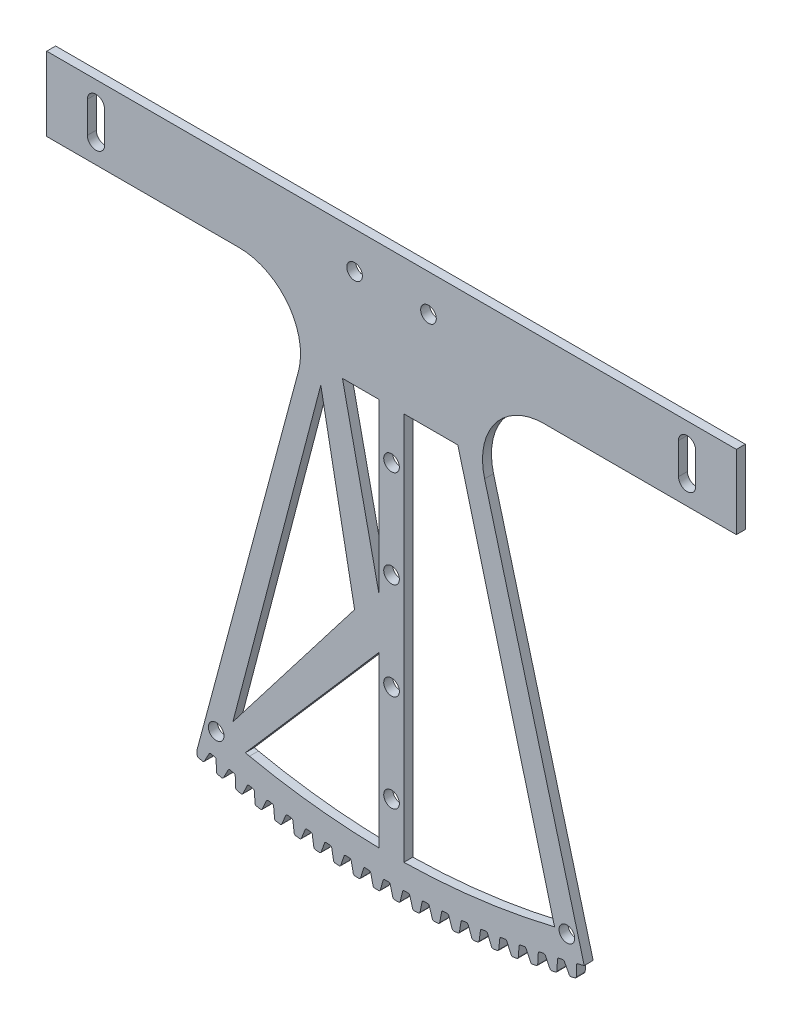
SolidWorks part; units mm, degrees
material "201 Annealed Stainless Steel (SS)"
ref_plane "Front Plane" through (0, 0, 0) normal (0, 0, 1) x (1, 0, 0)
ref_plane "Top Plane" through (0, 0, 0) normal (0, 1, 0) x (1, 0, 0)
ref_plane "Right Plane" through (0, 0, 0) normal (1, 0, 0) x (0, 0, -1)
sketch "Sketch3" plane through (0, 0, 0) normal (0, 0, 1) x (1, 0, 0)
  line L0 (0, 0) -> (0, -304.8) construction
  line L1 (-21.234, -79.2464) -> (-78.888, -294.4142)
  line L2 (21.234, -79.2464) -> (78.888, -294.4142)
  line L4 (-140, -79.56) -> (140, -79.56)
  line L5 (-140, -79.56) -> (-140, -109.56)
  line L6 (-140, -109.56) -> (140, -109.56)
  line L7 (140, -79.56) -> (140, -109.56)
  line L8 (0, -109.56) -> (0, -79.56) construction
  line L9 (-140, -94.56) -> (140, -94.56) construction
  arc A0 (-78.888, -294.4142) -> (78.888, -294.4142) centre (0, 0) ccw
  point P269 (0, -94.56)
  dimension "D1" = 304.8
  dimension "D4" = 79.56
  dimension "D5" = 30
  dimension "D6" = 280
  dimension "D7" = 140
extrude "Boss-Extrude2" add sketch "Sketch3" along normal blind 3.6286 contours L7 L4 L2 L6 | L1 L6 L2 L4 | L1 L4 L2 | L5 L6 L1 L4 | L1 A0 L2 L6 region at (0, -95.3531, 0) region at (-82.6452, -94.3847, 0) region at (0, -220.3694, 0) region at (82.6452, -94.3847, 0)
fillet "Fillet1" radius 25 2 edges at (-29.3565, -109.56, 1.8143) (29.3565, -109.56, 1.8143)
sketch "Sketch4" plane through (0, -79.56, 0) normal (0, 1, 0) x (1, 0, 0)
  line L1 (-140, 0) -> (140, 0)
  line L2 (-140, 0) -> (-140, -3.6286)
  line L3 (-140, -3.6286) -> (140, -3.6286)
  line L4 (140, 0) -> (140, -3.6286)
  line L5 (0, -3.6286) -> (0, 0) construction
  line L6 (-140, -1.8143) -> (140, -1.8143) construction
  point P252 (0, -1.8143)
sketch "Sketch5" plane through (0, 0, 0) normal (0, 0, -1) x (-1, 0, 0)
  line L0 (-123.5, -94.56) -> (-123.5, -100.91)
  line L1 (-116.5, -94.56) -> (-116.5, -100.91)
  line L2 (116.5, -94.56) -> (116.5, -88.21)
  line L3 (140, -79.56) -> (-140, -79.56) construction
  line L4 (-120, -88.21) -> (-120, -100.91) construction
  line L5 (0, -79.56) -> (0, -109.56) construction
  line L6 (-116.5, -94.56) -> (-116.5, -88.21)
  line L7 (-123.5, -94.56) -> (-123.5, -88.21)
  line L8 (116.5, -94.56) -> (116.5, -100.91)
  line L9 (123.5, -94.56) -> (123.5, -100.91)
  line L10 (123.5, -94.56) -> (123.5, -88.21)
  line L11 (-140, -79.56) -> (-140, -109.56) construction
  line L12 (120, -88.21) -> (120, -100.91) construction
  arc A1 (-116.5, -88.21) -> (-123.5, -88.21) centre (-120, -88.21) ccw
  arc A2 (-123.5, -100.91) -> (-116.5, -100.91) centre (-120, -100.91) ccw
  arc A3 (123.5, -100.91) -> (116.5, -100.91) centre (120, -100.91) cw
  arc A4 (116.5, -88.21) -> (123.5, -88.21) centre (120, -88.21) cw
  circle A5 centre (-15, -94.56) radius 3.175
  circle A6 centre (15, -94.56) radius 3.175
  dimension "D1" = 16.5
  dimension "D2" = 7
  dimension "D3" = 8.65
  dimension "D5" = 3.5
  dimension "D6" = 15
  dimension "D8" = 6.35
  dimension "D4" = 6.35
  dimension "D7" = 15
sketch "Sketch13" plane through (0, 0, 0) normal (0, 0, -1) x (-1, 0, 0)
  line L0 (0, 0) -> (78.888, -294.4142)
  line L1 (0, 0) -> (-78.888, -294.4142)
  arc A0 (-78.888, -294.4142) -> (78.888, -294.4142) centre (0, 0) ccw
  arc A1 (-78.888, -294.4142) -> (78.888, -294.4142) centre (0, 0) ccw construction
  arc A2 (-78.888, -294.4142) -> (78.888, -294.4142) centre (0, 0) ccw
  circle A3 centre (0, 0) radius 304.8
  dimension "D1" = 609.6
sketch "Sketch14" plane through (0, 0, 0) normal (0, 0, -1) x (-1, 0, 0)
  line L0 (0, 0) -> (80.0203, -298.6399) construction
  line L2 (78.888, -294.4142) -> (78.9109, -297.0369)
  line L3 (78.9109, -297.0369) -> (76.2891, -297.7211)
  line L18 (76.2891, -297.7211) -> (75.0275, -295.4216)
  line L20 (0, 0) -> (-79.2746, -295.8555) construction
  line L32 (78.888, -294.4142) -> (75.0275, -295.4216)
  line L33 (75.0275, -295.4216) -> (78.888, -294.4142)
  line L34 (0, 0) -> (-75.3952, -296.8678) construction
  line L35 (0, 0) -> (-71.5028, -297.8293) construction
  line L36 (0, 0) -> (-67.5982, -298.7397) construction
  line L37 (0, 0) -> (-63.6821, -299.5989) construction
  line L38 (0, 0) -> (-59.755, -300.4068) construction
  line L39 (0, 0) -> (-55.8176, -301.1633) construction
  line L40 (0, 0) -> (-51.8707, -301.8681) construction
  line L41 (0, 0) -> (-47.9149, -302.5212) construction
  line L42 (0, 0) -> (-43.951, -303.1225) construction
  line L43 (0, 0) -> (-39.9794, -303.6718) construction
  line L44 (0, 0) -> (-36.0011, -304.1691) construction
  line L45 (0, 0) -> (-32.0165, -304.6143) construction
  line L46 (0, 0) -> (-28.0265, -305.0073) construction
  line L47 (0, 0) -> (-24.0316, -305.348) construction
  line L48 (0, 0) -> (-20.0327, -305.6364) construction
  line L49 (0, 0) -> (-16.0303, -305.8724) construction
  line L50 (0, 0) -> (-12.0252, -306.0561) construction
  line L51 (0, 0) -> (-8.018, -306.1873) construction
  line L52 (0, 0) -> (-4.0094, -306.266) construction
  line L53 (0, 0) -> (-0.0002, -306.2922) construction
  line L54 (0, 0) -> (4.0091, -306.266) construction
  line L55 (0, 0) -> (8.0176, -306.1873) construction
  line L56 (0, 0) -> (12.0248, -306.0561) construction
  line L57 (0, 0) -> (16.03, -305.8725) construction
  line L58 (0, 0) -> (20.0323, -305.6364) construction
  line L59 (0, 0) -> (24.0313, -305.348) construction
  line L60 (0, 0) -> (28.0261, -305.0073) construction
  line L61 (0, 0) -> (32.0162, -304.6143) construction
  line L62 (0, 0) -> (36.0007, -304.1691) construction
  line L63 (0, 0) -> (39.9791, -303.6719) construction
  line L64 (0, 0) -> (43.9506, -303.1225) construction
  line L65 (0, 0) -> (47.9146, -302.5213) construction
  line L66 (0, 0) -> (51.8704, -301.8682) construction
  line L67 (0, 0) -> (55.8173, -301.1633) construction
  line L68 (0, 0) -> (59.7546, -300.4069) construction
  line L69 (0, 0) -> (63.6817, -299.599) construction
  line L70 (0, 0) -> (67.5979, -298.7398) construction
  line L71 (0, 0) -> (71.5025, -297.8293) construction
  line L72 (0, 0) -> (75.3948, -296.8679) construction
  line L73 (0, 0) -> (-79.2746, -295.8555) construction
  line L74 (0, 0) -> (-75.3952, -296.8678) construction
  line L137 (37.789, -141.0305) -> (78.888, -294.4142) construction
  line L138 (-140, -79.56) -> (-140, -109.56)
  line L139 (-140, -109.56) -> (-61.9371, -109.56)
  line L140 (-37.789, -141.0305) -> (-78.888, -294.4142)
  line L141 (78.888, -294.4142) -> (37.789, -141.0305)
  line L142 (61.9371, -109.56) -> (140, -109.56)
  line L143 (140, -109.56) -> (140, -79.56)
  line L144 (140, -79.56) -> (-140, -79.56)
  line L145 (-140, -79.56) -> (-140, -109.56)
  line L146 (-140, -109.56) -> (-61.9371, -109.56)
  line L147 (-37.789, -141.0305) -> (-78.888, -294.4142)
  line L149 (61.9371, -109.56) -> (140, -109.56)
  line L150 (140, -109.56) -> (140, -79.56)
  line L151 (140, -79.56) -> (-140, -79.56)
  circle A0 centre (0, 0) radius 307.34
  circle A1 centre (0, 0) radius 302.26
  arc A3 (-37.789, -141.0305) -> (-61.9371, -109.56) centre (-61.9371, -134.56) ccw
  arc A5 (61.9371, -109.56) -> (37.789, -141.0305) centre (61.9371, -134.56) ccw
  arc A6 (-37.789, -141.0305) -> (-61.9371, -109.56) centre (-61.9371, -134.56) ccw
  arc A8 (61.9371, -109.56) -> (37.789, -141.0305) centre (61.9371, -134.56) ccw
  arc A11 (-78.888, -294.4142) -> (78.888, -294.4142) centre (0, 0) ccw
  arc A12 (-78.888, -294.4142) -> (78.888, -294.4142) centre (0, 0) ccw
  arc M181 (-78.888, -294.4142) -> (78.888, -294.4142) centre (0, 0) ccw
  dimension "D5" = 614.68
  dimension "D6" = 30
  dimension "D7" = 40
  dimension "D4" = 604.52
  dimension "D1" = 14.5
  dimension "D3" = 14.5
  dimension "D8" = 0.75
  dimension "D9" = 306.2922
  dimension "D10" = 0.75
  dimension "D2" = 0
extrude "Boss-Extrude4" add sketch "Sketch14" against normal up to surface (3.6286 mm away) contours L2 M181 region at (-77.2591, -296.0724, 0) up to face at (0, -146.6727, 3.6286)
sketch "Sketch15" plane through (0, 0, 0) normal (1, 0, 0) x (0, 0, -1)
  line L0 (0, 0) -> (-23.3364, 0) construction
sketch "Sketch16" plane through (0, 0, 0) normal (0, 0, -1) x (-1, 0, 0)
  line L0 (75.0275, -295.4216) -> (73.7653, -293.1208)
  line L1 (73.7653, -293.1208) -> (71.1999, -293.7544)
  line L2 (71.1999, -293.7544) -> (71.1541, -296.3784)
  line L3 (0, 0) -> (71.5025, -297.8293) construction
  line L4 (0, 0) -> (75.3948, -296.8679) construction
  circle A0 centre (0, 0) radius 302.26 construction
  arc A1 (-78.888, -294.4142) -> (78.888, -294.4142) centre (0, 0) ccw construction
  dimension "D1" = 14.5
  dimension "D2" = 14.5
extrude "Cut-Extrude2" cut sketch "Sketch16" against normal through all and the other way through all
fillet "Fillet2" radius 0.7 2 edges at (-76.2891, -297.7211, 1.8143) (-78.9109, -297.0369, 1.8143)
pattern_circular "CirPattern8" count 20 every 1.5 about axis through (0, 0, 0) along (0, 0, 1) of "Cut-Extrude2", "Boss-Extrude4", "Fillet2"
extrude "Cut-Extrude3" cut sketch "Sketch5" against normal through all
sketch "Sketch17" plane through (0, 0, 0) normal (0, 0, -1) x (-1, 0, 0)
  line L0 (0, -79.56) -> (0, -134.56) construction
  line L1 (140, -79.56) -> (-140, -79.56) construction
  line L2 (-61.9371, -109.56) -> (61.9371, -109.56) construction
  line L3 (-36.9371, -134.56) -> (-26.9371, -134.56) construction
  line L4 (-36.9371, -134.56) -> (-26.9371, -134.56) construction
  line L5 (-26.9371, -134.56) -> (-66.1944, -284.3612) construction
  line L6 (-66.1944, -284.3612) -> (-76.1944, -284.3612) construction
  line L7 (0, -292.2593) -> (5, -292.2593) construction
  line L8 (-37.789, -141.0305) -> (-78.888, -294.4142) construction
  line L9 (0, -134.56) -> (-5, -134.56) construction
  line L10 (0, -134.56) -> (5, -134.56) construction
  line L11 (26.9371, -134.56) -> (36.9371, -134.56) construction
  line L12 (-5, -134.56) -> (-5, -292.2593) construction
  line L13 (36.9371, -134.56) -> (26.9371, -134.56) construction
  line L14 (26.9371, -134.56) -> (66.1944, -284.3612) construction
  line L15 (66.1944, -284.3612) -> (76.1944, -284.3612) construction
  line L16 (37.789, -141.0305) -> (78.888, -294.4142) construction
  line L17 (0.6571, -302.2593) -> (-3.5916, -302.2593) construction
  line L18 (-5, -134.56) -> (5, -134.56) construction
  line L19 (-3.5916, -292.2593) -> (-5, -292.2593) construction
  line L20 (5, -134.56) -> (5, -292.2593) construction
  line L21 (-3.5916, -302.2593) -> (-3.5916, -292.2593) construction
  line L22 (0, -193.6972) -> (0, -233.1221) construction
  line L23 (64.4199, -277.5899) -> (15, -213.4096)
  line L24 (-66.1944, -284.3612) -> (-68.6354, -294.3612) construction
  line L25 (-67.3487, -294.6613) -> (-69.9221, -294.0612) construction
  line L26 (71.1999, -293.7544) -> (66.067, -294.9513) construction
  line L27 (66.1944, -284.3612) -> (68.6335, -294.3529) construction
  line L28 (26.9371, -134.56) -> (66.1944, -284.3612)
  line L29 (26.9371, -134.56) -> (5, -134.56)
  line L30 (5, -134.56) -> (5, -292.2593)
  line L31 (-66.1944, -284.3612) -> (-26.9371, -134.56)
  line L32 (-26.9371, -134.56) -> (-5, -134.56)
  line L33 (-5, -134.56) -> (-5, -292.2593)
  line L34 (15, -213.4096) -> (28.7117, -141.3313)
  line L35 (66.1944, -284.3612) -> (57.6779, -286.2946)
  line L36 (66.1944, -284.3612) -> (64.4199, -277.5899) construction
  line L37 (5, -223.4096) -> (59.3729, -285.9321)
  line L41 (26.9371, -134.56) -> (28.7117, -141.3313) construction
  line L42 (26.9371, -134.56) -> (19.9371, -134.56) construction
  line L44 (28.7117, -141.3313) -> (26.9371, -134.56) construction
  line L47 (5, -203.4096) -> (19.9371, -134.56)
  circle A0 centre (0, -272.5469) radius 3.175
  arc A1 (61.9371, -109.56) -> (37.789, -141.0305) centre (61.9371, -134.56) ccw construction
  arc A2 (-37.789, -141.0305) -> (-61.9371, -109.56) centre (-61.9371, -134.56) ccw construction
  arc A3 (-66.1944, -284.3612) -> (-5, -292.2593) centre (0, -12.5018) ccw
  arc A4 (5, -292.2593) -> (66.1944, -284.3612) centre (0, -12.5018) ccw
  circle A5 centre (0, -233.1221) radius 3.175
  circle A6 centre (0, -193.6972) radius 3.175
  circle A7 centre (0, -154.2724) radius 3.175
  circle A8 centre (-71.1944, -284.3612) radius 3.175
  circle A9 centre (71.1944, -284.3612) radius 3.175
  arc A13 (19.9371, -134.56) -> (28.7117, -141.3313) centre (26.9371, -134.56) ccw construction
  arc A14 (19.9371, -134.56) -> (28.7117, -141.3313) centre (26.9371, -134.56) ccw construction
  arc A15 (-59.3729, -285.9321) -> (-64.4199, -277.5899) centre (-66.1944, -284.3612) ccw construction
  arc A16 (-64.4199, -277.5899) -> (-59.3729, -285.9321) centre (-66.1944, -284.3612) cw
  arc A17 (-5, -203.4096) -> (-5, -223.4096) centre (-5, -213.4096) ccw construction
  arc A18 (-28.7117, -141.3313) -> (-19.9371, -134.56) centre (-26.9371, -134.56) ccw construction
  arc A19 (5, -223.4096) -> (5, -203.4096) centre (5, -213.4096) ccw construction
  arc A20 (64.4199, -277.5899) -> (59.3729, -285.9321) centre (66.1944, -284.3612) ccw construction
  dimension "D13" = 6.35
  dimension "D14" = 6.35
  dimension "D15" = 10
  dimension "D16" = 7
  dimension "D17" = 7
  dimension "D20" = 7
  dimension "D21" = 10
  dimension "D22" = 7
  dimension "D18" = 7
  dimension "D1" = 10
  dimension "D2" = 5
  dimension "D3" = 10
  dimension "D4" = 10
  dimension "D5" = 5
  dimension "D6" = 5
  dimension "D7" = 10
  dimension "D8" = 10
  dimension "D9" = 5
  dimension "D10" = 10
  dimension "D11" = 157.6993
  dimension "D12" = 10
extrude "Cut-Extrude4" cut sketch "Sketch17" against normal through all contours L31 | L34 L23 L28 | L30 A4 L35 L37 | A3 L33 | L30 L47 L29 | L33 L32 | A6 | A7 | A5 | A0 | A9 | A8 region at (-36.0438, -210.777, 0) region at (-23.3567, -267.7722, 0) region at (-9.979, -157.5099, 0) region at (62.5855, -282.1856, 0) region at (27.141, -224.0716, 0) region at (0, -272.5469, 0) region at (0, -233.1221, 0) region at (0, -193.6972, 0) region at (0, -154.2724, 0) region at (71.1944, -284.3612, 0) region at (-71.1944, -284.3612, 0)
fillet "Fillet3" radius 0.7 39 edges at (75.039, -292.7973, 1.8143) (69.9221, -294.0612, 1.8143) (67.3487, -294.6613, 1.8143) (62.2005, -295.7908, 1.8143) (59.6123, -296.3233, 1.8143) (54.4363, -297.3177, 1.8143) (51.835, -297.7822, 1.8143) (46.6348, -298.6408, 1.8143) (44.0223, -299.037, 1.8143) (38.8013, -299.7592, 1.8143) (36.1793, -300.0869, 1.8143) (30.9412, -300.6722, 1.8143) (28.3115, -300.9312, 1.8143) (23.06, -301.3791, 1.8143) (20.4244, -301.5692, 1.8143) (15.1629, -301.8794, 1.8143) (12.5232, -302.0005, 1.8143) (7.2554, -302.1729, 1.8143) (4.6135, -302.2248, 1.8143) (-0.6571, -302.2593, 1.8143) (-3.2994, -302.242, 1.8143) (-8.5691, -302.1385, 1.8143) (-11.2101, -302.0521, 1.8143) (-16.4752, -301.8107, 1.8143) (-19.113, -301.6551, 1.8143) (-24.37, -301.276, 1.8143) (-27.0029, -301.0514, 1.8143) (-32.2482, -300.5348, 1.8143) (-34.8743, -300.2414, 1.8143) (-40.1042, -299.5877, 1.8143) (-42.7217, -299.2256, 1.8143) (-47.9327, -298.4352, 1.8143) (-50.5399, -298.0047, 1.8143) (-55.7284, -297.0782, 1.8143) (-58.3234, -296.5796, 1.8143) (-63.4859, -295.5176, 1.8143) (-66.067, -294.9513, 1.8143) (-71.1999, -293.7544, 1.8143) (-73.7653, -293.1208, 1.8143)
sketch "Sketch18" plane through (0, 0, 3.6286) normal (0, 0, 1) x (1, 0, 0)
  line L0 (37.789, -141.0305) -> (78.8881, -294.4142) construction
  line L1 (78.2307, -291.9607) -> (79.7961, -295.0297)
  line L2 (79.7961, -295.0297) -> (77.7182, -295.1502)
  line L3 (77.7182, -295.1502) -> (77.5958, -292.1301)
  arc A0 (77.5958, -292.1301) -> (78.2307, -291.9607) centre (0, 0) ccw
extrude "Cut-Extrude5" cut sketch "Sketch18" against normal blind 10
equation "\"D7@Sketch3\"=\"D6@Sketch3\"/2"
